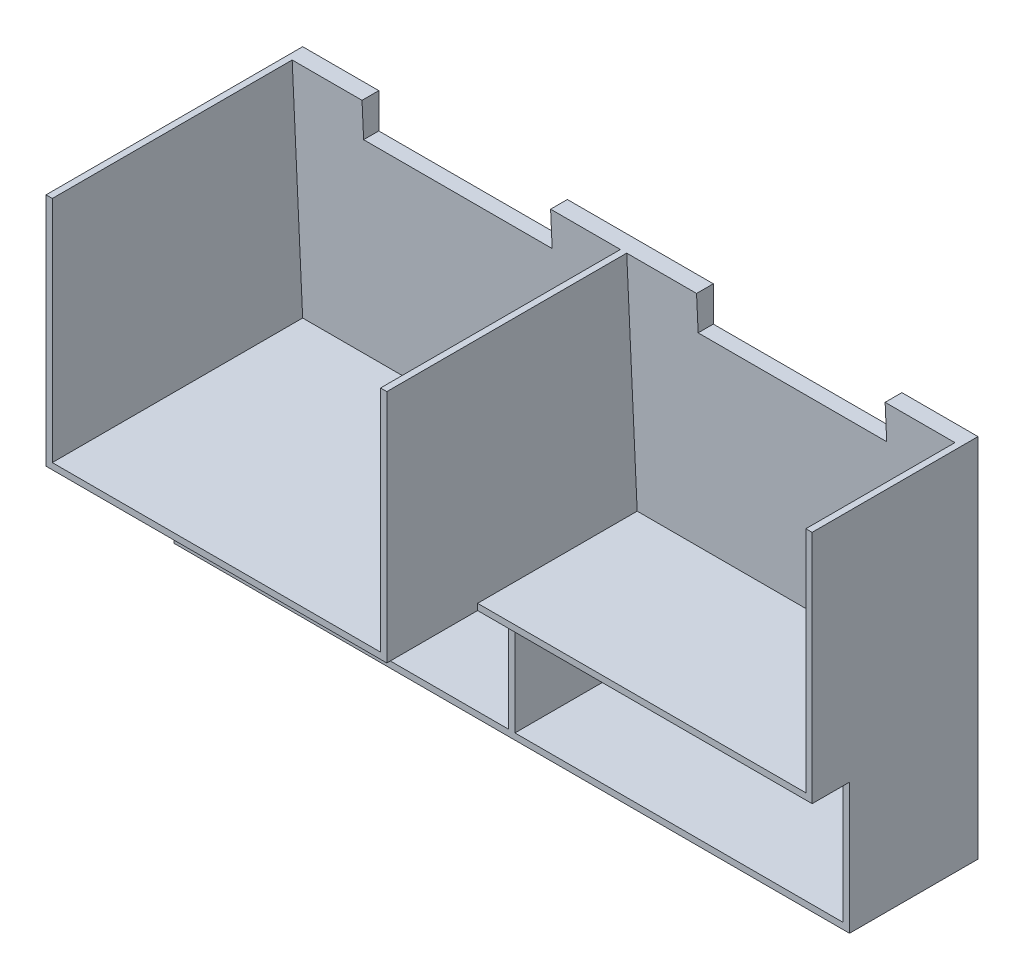
SolidWorks part; units mm, degrees
ref_plane "Front Plane" through (0, 0, 0) normal (0, 0, 1) x (1, 0, 0)
ref_plane "Top Plane" through (0, 0, 0) normal (0, 1, 0) x (1, 0, 0)
ref_plane "Right Plane" through (0, 0, 0) normal (1, 0, 0) x (0, 0, -1)
sketch "Sketch1" plane through (0, 0, 0) normal (0, 0, 1) x (1, 0, 0)
  line L9 (0, 0) -> (193.4, 0)
  line L10 (0, 0) -> (0, 104.8)
  line L11 (0, 104.8) -> (193.4, 104.8)
  line L12 (193.4, 0) -> (193.4, 104.8)
  line L13 (1.8, 104.8) -> (95.8, 104.8)
  line L14 (1.8, 104.8) -> (1.8, 39.3)
  line L15 (1.8, 39.3) -> (95.8, 39.3)
  line L16 (95.8, 104.8) -> (95.8, 39.3)
  line L17 (97.6, 104.8) -> (191.6, 104.8)
  line L18 (97.6, 104.8) -> (97.6, 39.3)
  line L19 (97.6, 39.3) -> (191.6, 39.3)
  line L20 (191.6, 104.8) -> (191.6, 39.3)
  line L21 (1.8, 37.5) -> (95.8, 37.5)
  line L22 (1.8, 37.5) -> (1.8, 1.8)
  line L23 (1.8, 1.8) -> (95.8, 1.8)
  line L24 (95.8, 37.5) -> (95.8, 1.8)
  line L25 (97.6, 37.5) -> (191.6, 37.5)
  line L26 (97.6, 37.5) -> (97.6, 1.8)
  line L27 (97.6, 1.8) -> (191.6, 1.8)
  line L28 (191.6, 37.5) -> (191.6, 1.8)
  line L29 (21.8, 104.8) -> (75.8, 104.8)
  line L30 (21.8, 104.8) -> (21.8, 94.8)
  line L31 (21.8, 94.8) -> (75.8, 94.8)
  line L32 (75.8, 104.8) -> (75.8, 94.8)
  line L33 (117.6, 104.8) -> (171.6, 104.8)
  line L34 (117.6, 104.8) -> (117.6, 94.8)
  line L35 (117.6, 94.8) -> (171.6, 94.8)
  line L36 (171.6, 104.8) -> (171.6, 94.8)
  line L37 (97.6, 37.5) -> (95.8, 37.5)
  line L38 (97.6, 37.5) -> (97.6, 39.3)
  line L39 (97.6, 39.3) -> (95.8, 39.3)
  line L40 (95.8, 37.5) -> (95.8, 39.3)
  line L41 (1.8, 37.5) -> (0, 37.5)
  line L42 (1.8, 37.5) -> (1.8, 39.3)
  line L43 (1.8, 39.3) -> (0, 39.3)
  line L44 (0, 37.5) -> (0, 39.3)
  line L45 (191.6, 37.5) -> (193.4, 37.5)
  line L46 (191.6, 37.5) -> (191.6, 39.3)
  line L47 (191.6, 39.3) -> (193.4, 39.3)
  line L48 (193.4, 37.5) -> (193.4, 39.3)
  dimension "D1" = 104.8
  dimension "D2" = 193.4
  dimension "D3" = 65.5
  dimension "D4" = 1.8
  dimension "D5" = 1.8
  dimension "D6" = 1.8
  dimension "D7" = 1.8
  dimension "D8" = 1.8
  dimension "D9" = 20
  dimension "D10" = 20
  dimension "D11" = 20
  dimension "D12" = 10
extrude "Boss-Extrude1" add sketch "Sketch1" against normal blind 1.8 contours L24 L21 L22 L23 | L11 L32 L31 L30 L14 L15 L16 | L28 L25 L26 L27 | L11 L36 L35 L34 L18 L19 L20 | L11 L20 L19 L18 L16 L15 L14 L10 L9 L12 L21 L24 L23 L22 L25 L28 L27 L26 | L43 L14 L11 L10 | L42 L43 L10 L41 | L39 L18 L11 L16 | L40 L37 L38 L39 | L42 L21 L40 L15 | L47 L46 L45 L12 | L20 L47 L12 L11 | L25 L46 L19 L38 | L36 L17 L34 L35 | L32 L13 L30 L31 region at (96.7, 7.5826, 0) region at (0.9, 38.4, 0) region at (192.5, 38.4, 0) region at (0.9, 72.05, 0) region at (48.8, 38.4, 0) region at (48.8, 19.65, 0) region at (192.5, 72.05, 0) region at (144.6, 19.65, 0) region at (144.6, 38.4, 0) region at (48.8, 69.3822, 0) region at (96.7, 38.4, 0) region at (144.6, 69.3822, 0) region at (96.7, 72.05, 0) region at (48.8, 99.8, 0) region at (144.6, 99.8, 0)
extrude "Boss-Extrude2" add sketch "Sketch1<8>" along normal blind 71.7 contours L39 L18 L11 L16 | L40 L37 L38 L39 | L42 L21 L40 L15 | L43 L14 L11 L10 | L42 L43 L10 L41 region at (0.9, 38.4, 0) region at (0.9, 72.05, 0) region at (48.8, 38.4, 0) region at (96.7, 38.4, 0) region at (96.7, 72.05, 0)
sketch "Sketch1<8>" plane through (0, 0, 0) normal (0, 0, 1) x (1, 0, 0) same geometry as "Sketch1"
extrude "Boss-Extrude3" add sketch "Sketch1<10>" along normal blind 45.7 contours L25 L46 L19 L38 | L20 L47 L12 L11 | L47 L46 L45 L12 region at (192.5, 38.4, 0) region at (192.5, 72.05, 0) region at (144.6, 38.4, 0)
sketch "Sketch1<10>" plane through (0, 0, 0) normal (0, 0, 1) x (1, 0, 0) same geometry as "Sketch1"
extrude "Boss-Extrude4" add sketch "Sketch1<11>" along normal blind 35 contours L45 L28 L27 L26 L37 L24 L23 L22 L41 L10 L9 L12 region at (96.7, 7.5826, 0)
sketch "Sketch1<11>" plane through (0, 0, 0) normal (0, 0, 1) x (1, 0, 0) same geometry as "Sketch1"
sketch "Sketch2" plane through (191.6, 0, 0) normal (-1, 0, 0) x (0, 0, 1)
  line L0 (45.7, 39.3) -> (0, 39.3) construction
  line L1 (0, 104.8) -> (3, 104.8)
  line L2 (0, 104.8) -> (0, 39.3)
  line L3 (0, 39.3) -> (3, 39.3)
  line L4 (3, 104.8) -> (3, 39.3)
  line L5 (0, 104.8) -> (0, 39.3) construction
  line L6 (3, 104.8) -> (0, 39.3)
  line M2 (0, 104.8) -> (0, 39.3)
  line M5 (45.7, 104.8) -> (0, 104.8)
  dimension "D1" = 3
extrude "Boss-Extrude8" add sketch "Sketch2" along normal up to surface (189.8 mm away) contours L6 M5 M2 region at (191.6, 82.9667, 1) up to face at (1.8, 72.05, 35.85)
extrude "Cut-Extrude1" cut sketch "Sketch1<12>" along normal blind 27 and the other way blind 16 contours L36 L17 L34 L35 | L32 L13 L30 L31 region at (48.8, 99.8, 0) region at (144.6, 99.8, 0)
sketch "Sketch1<12>" plane through (0, 0, 0) normal (0, 0, 1) x (1, 0, 0) same geometry as "Sketch1"
equation "\"padding\"=1.8"
equation "\"D4@Sketch1\"=\"padding\""
equation "\"D5@Sketch1\"=\"padding\""
equation "\"D6@Sketch1\"=\"padding\""
equation "\"D7@Sketch1\"=\"padding\""
equation "\"D8@Sketch1\"=\"padding\""
equation "\"D1@Boss-Extrude1\"=\"padding\""
